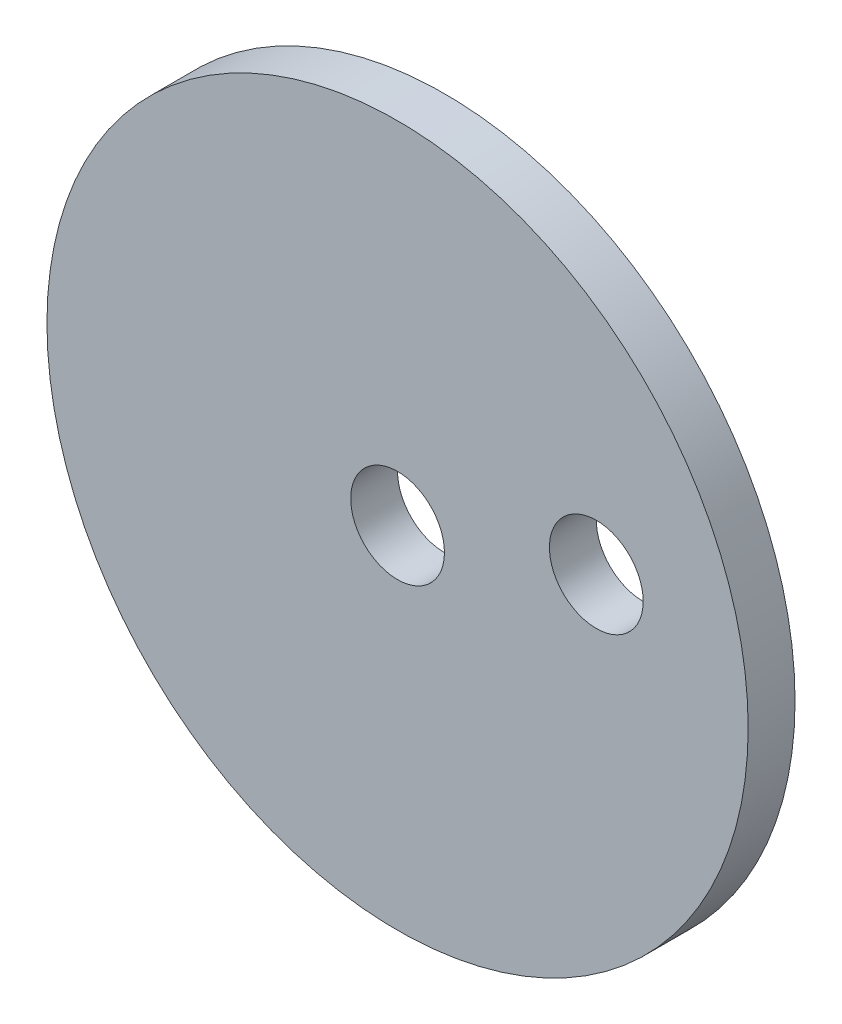
SolidWorks part; units mm, degrees
ref_plane "Front Plane" through (0, 0, 0) normal (0, 0, 1) x (1, 0, 0)
ref_plane "Top Plane" through (0, 0, 0) normal (0, 1, 0) x (1, 0, 0)
ref_plane "Right Plane" through (0, 0, 0) normal (1, 0, 0) x (0, 0, -1)
sketch "Sketch1" plane through (0, 0, 0) normal (0, 0, 1) x (1, 0, 0)
  circle A0 centre (0, 0) radius 47.498
  circle A1 centre (0, 0) radius 6.35
  circle A2 centre (26.9215, 7.7318) radius 6.35
  dimension "D1" = 94.996
  dimension "D2" = 12.7
  dimension "D3" = 12.7
extrude "Boss-Extrude1" add sketch "Sketch1" along normal blind 6.35
